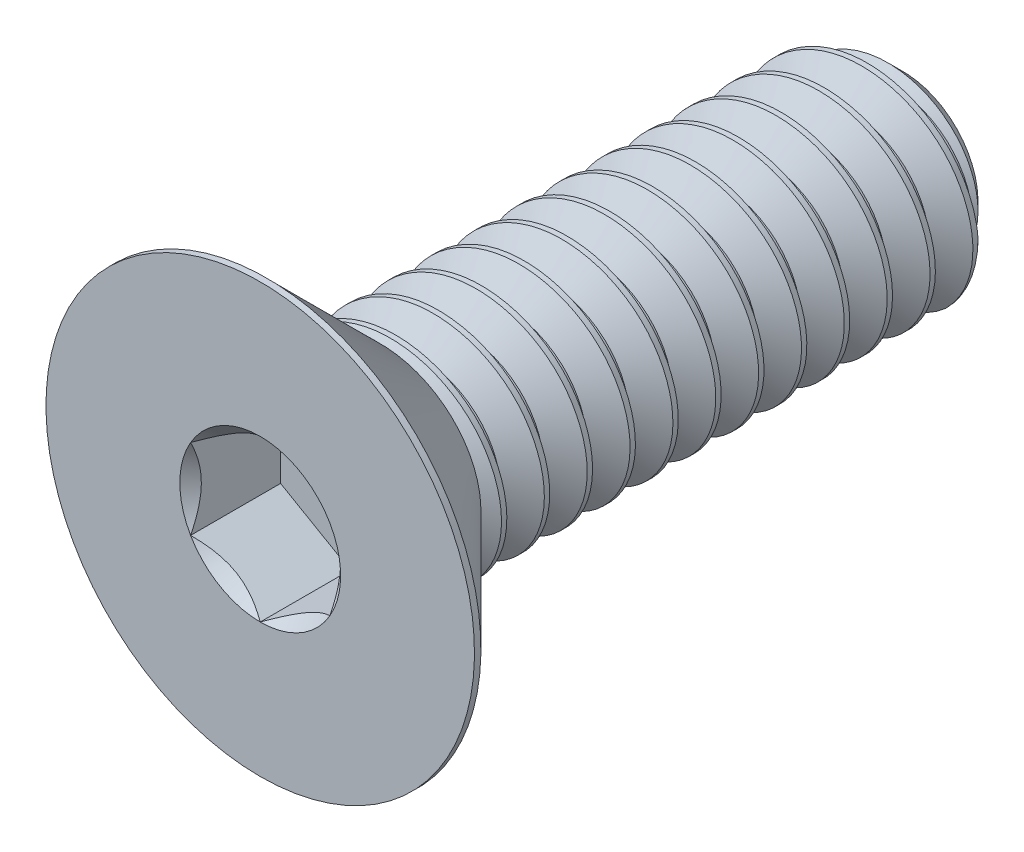
SolidWorks part; units mm, degrees
ref_plane "Front" through (0, 0, 0) normal (0, 0, 1) x (1, 0, 0)
ref_plane "Top" through (0, 0, 0) normal (0, 1, 0) x (1, 0, 0)
ref_plane "Right" through (0, 0, 0) normal (1, 0, 0) x (0, 0, -1)
sketch "Sketch11" plane through (0, 0, 0) normal (1, 0, 0) x (0, 0, -1)
  line L0 (-3, 2) -> (3, 2) construction
  line L5 (-3, 2) -> (-3, -2) construction
  line L6 (3, 1) -> (3, -1) construction
  line L7 (-2.99, 0.65) -> (-2.99, -0.65) construction
  line L8 (2.975, 1.0433) -> (3.375, 1.0433) construction
  line L9 (3.375, 1.0433) -> (3.175, 0.6969) construction
  line L10 (3.175, 0.6969) -> (2.975, 1.0433) construction
  line L11 (3.15, 0.7402) -> (3.2, 0.7402) construction
  line L12 (3.175, 0.7402) -> (3.175, 0.6969) construction
  line L13 (2.9875, 1.0217) -> (3.3625, 1.0217) construction
  line L14 (3.175, 1.0433) -> (3.175, 1) construction
  line L15 (3, 1) -> (3.35, 1) construction
  line L17 (-2.94, 2) -> (-0.94, 0) construction
  line L18 (-0.94, 0) -> (-2.94, -2) construction
  point P3 (-1.8, 2)
  point P8 (0, 2)
  point P21 (3.175, 1.0217)
  point P26 (-3, 0)
  point P28 (-2.99, 0)
  point P29 (3, 0)
  dimension "Length" = 6
  dimension "Head Diameter" = 4
  dimension "Thread Major Diameter" = 2
  dimension "Head Height" = 1.2
  dimension "Drive Size" = 1.3
  dimension "Thread Pitch" = 0.4
  dimension "D1" = 0.05
  dimension "D2" = 0.01
  dimension "D3" = 0.06
  dimension "Countersink Angle" = 90
sketch "Sketch1" plane through (0, 0, 0) normal (1, 0, 0) x (0, 0, -1)
  line L2 (-1.8, 1) -> (3, 1)
  line L3 (3, 1) -> (3, 0)
  line L4 (-2.16, 1) -> (-2.16, 0)
  line L5 (-1.8, 1) -> (-2.16, 1)
  line L6 (-3, 2) -> (-3, -2) construction
  line L7 (3, 1) -> (3, -1) construction
  line L8 (-2.16, 0) -> (3, 0)
  dimension "D1" = 0.84
revolve "Revolve1" add sketch "Sketch1" angle 360 mid plane about L8
chamfer "Chamfer1" distance 0.3 angle 45 1 edges at (0, -1, -3)
sketch "Sketch7" plane through (0, 0, 0) normal (1, 0, 0) x (0, 0, -1)
  line L2 (-3, 2) -> (-2.94, 2)
  line L5 (-1.8, 0.86) -> (-1.8, 0)
  line L6 (-3, 2) -> (-3, 0)
  line L8 (-3, 2) -> (-3, -2) construction
  line L9 (-3, 0) -> (-1.8, 0)
  line L12 (-2.94, 2) -> (-1.8, 0.86)
  line L13 (-2.94, 2) -> (-0.94, 0) construction
revolve "Revolve2" add sketch "Sketch7" angle 360 mid plane about L9 region at (0, 0.7698, 2.4817)
ref_plane "Plane1" through (0, 0, 1.8) normal (0, 0, 1) x (1, 0, 0)
sketch "Sketch5" plane through (0, 0, 3) normal (0, 0, 1) x (1, 0, 0)
  line L1 (0.65, -0.3753) -> (0.65, 0.3753)
  line L2 (0.65, 0.3753) -> (0, 0.7506)
  line L3 (0, 0.7506) -> (-0.65, 0.3753)
  line L4 (-0.65, 0.3753) -> (-0.65, -0.3753)
  line L5 (-0.65, -0.3753) -> (0, -0.7506)
  line L6 (0, -0.7506) -> (0.65, -0.3753)
  circle A0 centre (0, 0) radius 0.65 construction
extrude "Cut-Extrude2" cut sketch "Sketch5" against normal blind 0.84
sketch "Sketch6" plane through (0, 0, 3) normal (0, 0, -1) x (-1, 0, 0)
  circle A0 centre (0, 0) radius 0.7506
extrude "Cut-Extrude3" cut sketch "Sketch6" along normal blind 0.84 draft 45
sketch "Sketch12" plane through (0, 0, -3) normal (0, 0, -1) x (-1, 0, 0)
  circle A0 centre (0, 0) radius 1 construction
  circle A1 centre (0, 0) radius 1
curve "Helix/Spiral1" pitch 0.4 height 6 radius 1 centre (0, 0, -3) axis (0, 0, 1) start towards (0, 1, 0)
sketch "Sketch13" plane through (0, 0, 0) normal (1, 0, 0) x (0, 0, -1)
  line L0 (2.9875, 1.0217) -> (3.3625, 1.0217)
  line L1 (3.3625, 1.0217) -> (3.2, 0.7402)
  line L2 (3.2, 0.7402) -> (3.15, 0.7402)
  line L3 (3.15, 0.7402) -> (2.9875, 1.0217)
sweep "Cut-Sweep1" cut profiles "Sketch13" path "Helix/Spiral1" align with end faces yes
combine bodies "Combine1" operation type add bodies to combine 113 127
equation "\"D1@Chamfer1\"=\"Thread Pitch@Sketch11\" * .75"
equation "\"D1@Cut-Extrude2\"= \"Head Height@Sketch11\" * .7"
equation "\"D1@Cut-Extrude3\" = \"D1@Cut-Extrude2\""
equation "\"D1@Sketch11\"=\"Thread Pitch@Sketch11\"/8"
equation "\"D3@Sketch11\"=\"Head Height@Sketch11\"*.05"
equation "\"D4@Helix/Spiral1\"=\"Thread Pitch@Sketch11\""
equation "\"D1@Sketch1\"=\"Head Height@Sketch11\"*.7"
equation "\"D3@Helix/Spiral1\"=\"Length@Sketch11\""
